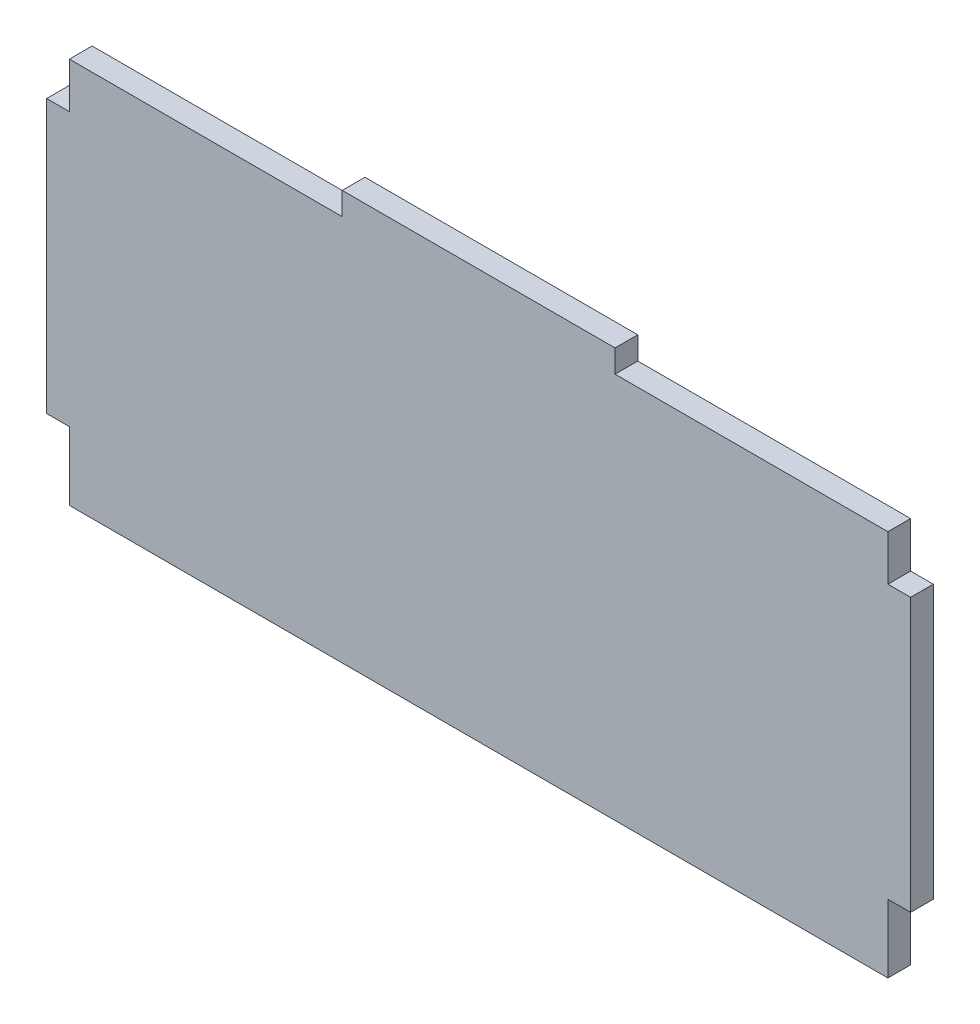
SolidWorks part; units mm, degrees
ref_plane "Front Plane" through (0, 0, 0) normal (0, 0, 1) x (1, 0, 0)
ref_plane "Top Plane" through (0, 0, 0) normal (0, 1, 0) x (1, 0, 0)
ref_plane "Right Plane" through (0, 0, 0) normal (1, 0, 0) x (0, 0, -1)
sketch "Sketch1" plane through (0, 0, 0) normal (0, 0, 1) x (1, 0, 0)
  line L0 (185.3837, 2.969) -> (185.3837, 43.298) construction
  line L1 (-49.5663, 19.0519) -> (179.0337, 19.0519)
  line L2 (-49.5663, 19.0519) -> (-49.5663, -88.8981)
  line L3 (-49.5663, -88.8981) -> (179.0337, -88.8981)
  line L4 (179.0337, 19.0519) -> (179.0337, -88.8981)
  line L5 (-55.9163, 6.3519) -> (-49.5663, 6.3519)
  line L6 (-55.9163, 6.3519) -> (-55.9163, -69.8481)
  line L7 (-55.9163, -69.8481) -> (-49.5663, -69.8481)
  line L8 (-49.5663, 6.3519) -> (-49.5663, -69.8481)
  line L9 (179.0337, 6.3519) -> (185.3837, 6.3519)
  line L10 (179.0337, 6.3519) -> (179.0337, -69.8481)
  line L11 (179.0337, -69.8481) -> (185.3837, -69.8481)
  line L12 (185.3837, 6.3519) -> (185.3837, -69.8481)
  line L13 (26.6337, 25.4019) -> (102.8337, 25.4019)
  line L14 (26.6337, 25.4019) -> (26.6337, 19.0519)
  line L15 (26.6337, 19.0519) -> (102.8337, 19.0519)
  line L16 (102.8337, 25.4019) -> (102.8337, 19.0519)
  dimension "D1" = 228.6
  dimension "D2" = 107.95
  dimension "D3" = 76.2
  dimension "D5" = 6.35
  dimension "D6" = 6.35
  dimension "D7" = 76.2
  dimension "D9" = 6.35
  dimension "D10" = 76.2
  dimension "D11" = 76.2
  dimension "D4" = 12.7
  dimension "D8" = 12.7
extrude "Boss-Extrude1" add sketch "Sketch1" along normal blind 6.35 contours L4 L1 L2 L3 | L16 L13 L14 L1 | L12 L9 L4 L11 | L6 L7 L2 L5 region at (64.7337, -34.9231, 0) region at (64.7337, 22.2269, 0) region at (-52.7413, -31.7481, 0) region at (182.2087, -31.7481, 0)
equation "\"width\"= 9in"
equation "\"Height\"= 18in"
equation "\"thick\"= 0.25"
equation "\"D1@Sketch1\"=\"width\""
equation "\"D2@Sketch1\"=(\"width\"/2)-\"thick\""
equation "\"D5@Sketch1\"=\"thick\""
equation "\"D6@Sketch1\"=\"thick\""
equation "\"D7@Sketch1\"=3"
equation "\"D9@Sketch1\"=\"thick\""
equation "\"D1@Boss-Extrude1\"=\"thick\""
equation "\"D4@Sketch1\"=0.75-\"thick\""
equation "\"D8@Sketch1\"=0.75-\"thick\""
